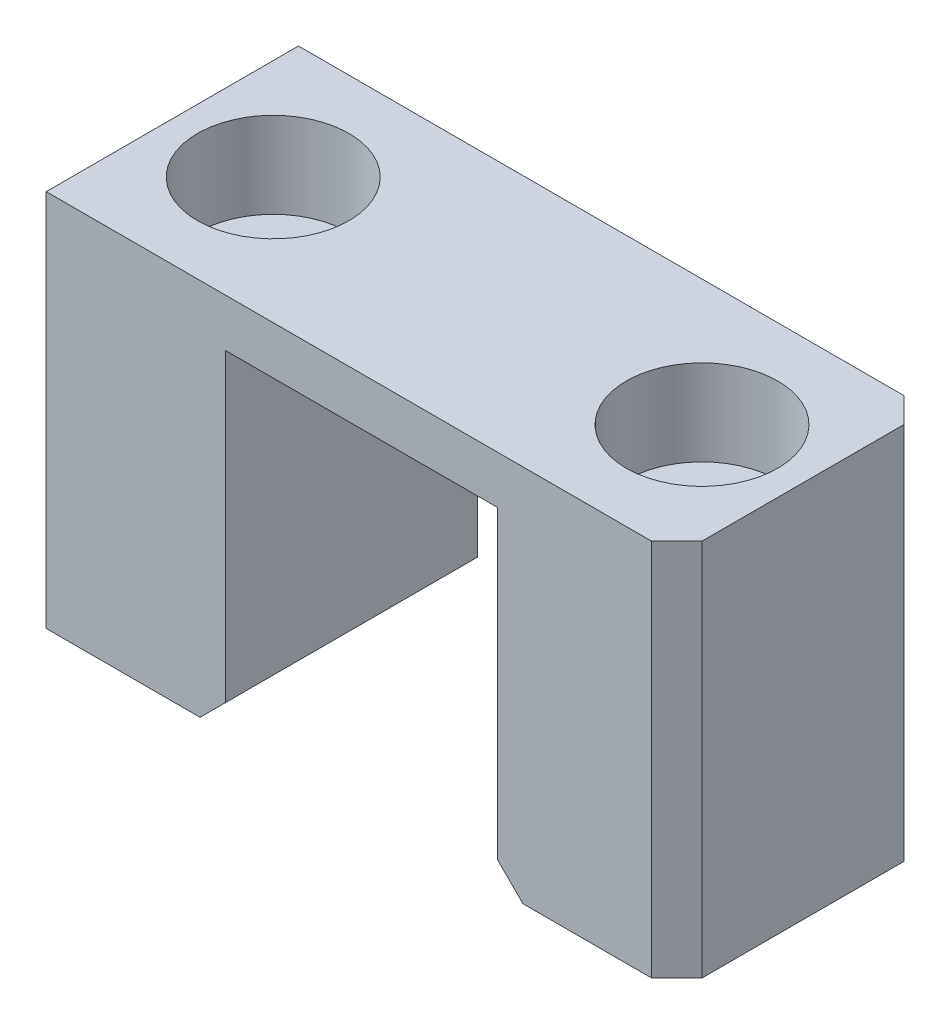
SolidWorks part; units mm, degrees
ref_plane "前视基准面" through (0, 0, 0) normal (0, 0, 1) x (1, 0, 0)
ref_plane "上视基准面" through (0, 0, 0) normal (0, 1, 0) x (1, 0, 0)
ref_plane "右视基准面" through (0, 0, 0) normal (1, 0, 0) x (0, 0, -1)
sketch "草图1" plane through (0, 0, 0) normal (0, 0, 1) x (1, 0, 0)
  line L0 (-12.5, 0) -> (-12.5, 15)
  line L1 (-12.5, 15) -> (12.5, 15)
  line L2 (12.5, 15) -> (12.5, 0)
  line L3 (12.5, 0) -> (5.4, 0)
  line L4 (5.4, 0) -> (5.4, 13.1)
  line L5 (5.4, 13.1) -> (-5.4, 13.1)
  line L6 (-5.4, 13.1) -> (-5.4, 0)
  line L7 (-5.4, 0) -> (-12.5, 0)
  point P11 (0, 15)
  dimension "D1" = 25
  dimension "D2" = 10.8
  dimension "D3" = 15
  dimension "D4" = 13.1
extrude "凸台-拉伸1" add sketch "草图1" along normal mid plane 10
sketch "草图3" plane through (0, 15, 0) normal (0, 1, 0) x (1, 0, 0)
  line L0 (8.5, 0) -> (-8.5, 0)
  point P4 (0, 0)
  dimension "D1" = 17
hole_wizard "打孔尺寸(%根据)内六角圆柱头螺钉的类型1" positions "3D草图1" profile "草图4" counterbore size "M3" standard "GB" end condition up to next
sketch3d "3D草图1"
  point P0 (-8.5, 15, 0)
  point P3 (8.5, 15, 0)
sketch "草图4" plane through (-8.5, 15, 0) normal (1, 0, 0) x (0, 0, 1)
  line L0 (0, 0) -> (0, 15)
  line L1 (0, 15) -> (1.7, 15)
  line L3 (1.7, 15) -> (1.7, 3.4)
  line L4 (1.7, 3.4) -> (3, 3.4)
  line L5 (3, 3.4) -> (3, 0)
  line L7 (3, 0) -> (0, 0)
  line L11 (0, -6.35) -> (0, 107.95) construction
  dimension "通孔孔直径" = 3.4
  dimension "通孔孔深度" = 15
  dimension "柱形沉头孔直径" = 6
  dimension "柱形沉头孔深度" = 3.4
chamfer "倒角1" distance 1 angle 45 2 edges at (12.5, 7.5, -5) (12.5, 7.5, 5)
chamfer "倒角2" distance 1 angle 45 2 edges at (-5.4, 0, 0) (5.4, 0, 0)
